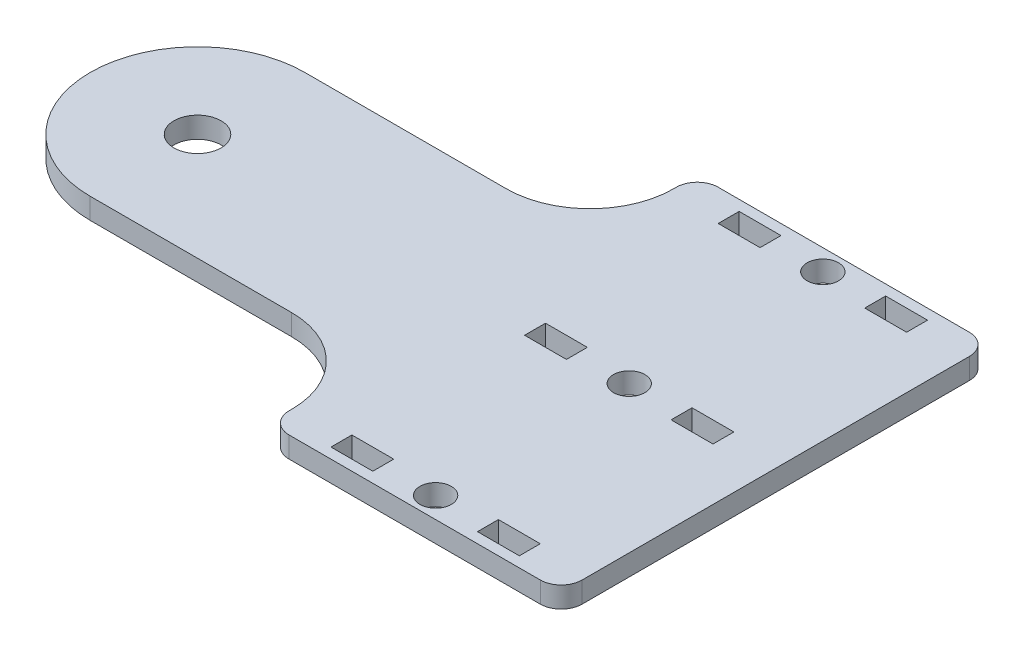
SolidWorks part; units mm, degrees
ref_plane "Front Plane" through (0, 0, 0) normal (0, 0, 1) x (1, 0, 0)
ref_plane "Top Plane" through (0, 0, 0) normal (0, 1, 0) x (1, 0, 0)
ref_plane "Right Plane" through (0, 0, 0) normal (1, 0, 0) x (0, 0, -1)
sketch "Sketch1" plane through (0, 0, 0) normal (0, 1, 0) x (1, 0, 0)
  line L0 (0, 10.25) -> (65.5, 10.25) construction
  line L1 (0, 0) -> (37.5, 0)
  line L2 (0, 0) -> (0, 20.5)
  line L3 (0, 20.5) -> (37.5, 20.5)
  line L4 (65.5, -0.75) -> (65.5, 21.25)
  line L5 (10.25, 10.25) -> (10.25, 20.5) construction
  line L8 (37.5, 0) -> (37.5, -10.25)
  line L10 (65.5, 21.25) -> (65.5, 30.75)
  line L11 (65.5, 30.75) -> (37.5, 30.75)
  line L12 (37.5, 20.5) -> (37.5, 30.75)
  line L13 (65.5, -10.25) -> (37.5, -10.25)
  line L14 (65.5, -0.75) -> (65.5, -10.25)
  circle A0 centre (10.25, 10.25) radius 2.25
  dimension "D3" = 4.5
  dimension "D4" = 20.5
  dimension "D5" = 10.25
  dimension "D6" = 55.25
  dimension "D7" = 41
  dimension "D8" = 28
extrude "Boss-Extrude1" add sketch "Sketch1" along normal blind 2
fillet "Fillet1" radius 10.25 2 edges at (0, 1, -20.5) (0, 1, 0)
fillet "Fillet2" radius 2 4 edges at (37.5, 1, -30.75) (65.5, 1, -30.75) (65.5, 1, 10.25) (37.5, 1, 10.25)
sketch "Sketch2" plane through (0, 2, 0) normal (0, 1, 0) x (1, 0, 0)
  line L0 (65.5, 10.25) -> (0, 10.25) construction
  line L1 (65.5, -8.25) -> (65.5, 28.75) construction
  line L2 (37.5, 28.75) -> (65.5, 28.75) construction
  line L3 (37.5, 28.75) -> (37.5, 20.5) construction
  line L15 (63.5, 30.75) -> (39.5, 30.75) construction
  line L17 (42.5, 27.75) -> (46.5, 27.75)
  line L18 (42.5, 27.75) -> (42.5, 29.75)
  line L19 (42.5, 29.75) -> (46.5, 29.75)
  line L20 (46.5, 27.75) -> (46.5, 29.75)
  line L21 (42.5, 27.75) -> (46.5, 29.75) construction
  line L22 (42.5, 29.75) -> (46.5, 27.75) construction
  line L23 (60.5, 27.75) -> (56.5, 27.75)
  line L24 (60.5, 27.75) -> (60.5, 29.75)
  line L25 (60.5, 29.75) -> (56.5, 29.75)
  line L26 (56.5, 27.75) -> (56.5, 29.75)
  line L27 (60.5, 27.75) -> (56.5, 29.75) construction
  line L28 (60.5, 29.75) -> (56.5, 27.75) construction
  line L37 (42.5, 9.25) -> (42.5, 11.25)
  line L38 (42.5, 9.25) -> (46.5, 9.25)
  line L39 (46.5, 9.25) -> (46.5, 11.25)
  line L40 (42.5, 11.25) -> (46.5, 11.25)
  line L41 (60.5, 9.25) -> (60.5, 11.25)
  line L42 (60.5, 9.25) -> (56.5, 9.25)
  line L43 (56.5, 9.25) -> (56.5, 11.25)
  line L44 (60.5, 11.25) -> (56.5, 11.25)
  line L53 (42.5, -9.25) -> (42.5, -7.25)
  line L54 (42.5, -9.25) -> (46.5, -9.25)
  line L55 (46.5, -9.25) -> (46.5, -7.25)
  line L56 (42.5, -7.25) -> (46.5, -7.25)
  line L57 (60.5, -9.25) -> (60.5, -7.25)
  line L58 (60.5, -9.25) -> (56.5, -9.25)
  line L59 (56.5, -9.25) -> (56.5, -7.25)
  line L60 (60.5, -7.25) -> (56.5, -7.25)
  circle A3 centre (51.5, 28.75) radius 1.5
  circle A4 centre (51.5, 10.25) radius 1.5
  circle A5 centre (51.5, -8.25) radius 1.5
  point P9 (26.5, 28.75)
  point P10 (58.5, 29.75)
  point P14 (35.5, 28.75)
  point P19 (44.5, 28.75)
  point P24 (58.5, 28.75)
  dimension "D11" = 3
  dimension "D12" = 5
  dimension "D2" = 4
  dimension "D3" = 1
  dimension "D5" = 5
  dimension "D6" = 10
  dimension "D8" = 3
extrude "Cut-Extrude1" cut sketch "Sketch2" against normal blind 2
fillet "Fillet3" radius 8 2 edges at (37.5, 1, 0) (37.5, 1, -20.5)
